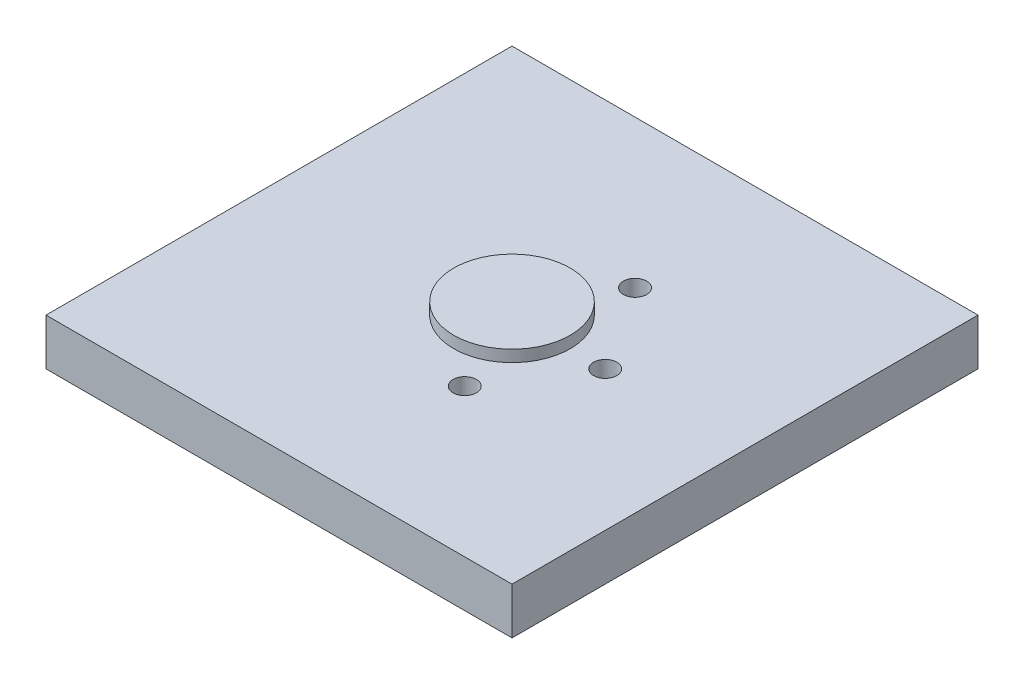
SolidWorks part; units mm, degrees
ref_plane "Front Plane" through (0, 0, 0) normal (0, 0, 1) x (1, 0, 0)
ref_plane "Top Plane" through (0, 0, 0) normal (0, 1, 0) x (1, 0, 0)
ref_plane "Right Plane" through (0, 0, 0) normal (1, 0, 0) x (0, 0, -1)
sketch "Sketch1" plane through (0, 0, 0) normal (0, 1, 0) x (1, 0, 0)
  line L1 (-63.5, 63.5) -> (63.5, 63.5)
  line L2 (-63.5, 63.5) -> (-63.5, -63.5)
  line L3 (-63.5, -63.5) -> (63.5, -63.5)
  line L4 (63.5, 63.5) -> (63.5, -63.5)
  line L5 (-63.5, 63.5) -> (63.5, -63.5) construction
  line L6 (-63.5, -63.5) -> (63.5, 63.5) construction
  point P0 (0, 0)
  dimension "D1" = 127
extrude "Boss-Extrude1" add sketch "Sketch1" along normal blind 12.7
sketch "Sketch3" plane through (0, 12.7, 0) normal (0, 1, 0) x (1, 0, 0)
  circle A0 centre (0, 0) radius 15.875
  dimension "D1" = 31.75
extrude "Boss-Extrude2" add sketch "Sketch3" along normal blind 3.175
hole_wizard "1/4 (0.25) Diameter Hole1" positions "Sketch5" profile "Sketch4" hole size "1/4" standard "ANSI Inch" end condition up to next
sketch "Sketch5" plane through (0, 12.7, 0) normal (0, 1, 0) x (1, 0, 0)
  line L0 (0, 0) -> (63.5, 0) construction
  line L1 (63.5, -63.5) -> (63.5, 63.5) construction
  line L4 (0, 0) -> (63.5, 142.6233) construction
  line L6 (0, 0) -> (63.5, -142.6233) construction
  circle A0 centre (0, 0) radius 25.4 construction
  point P0 (10.3311, 23.2041)
  point P2 (25.4, 0)
  point P4 (10.3311, -23.2041)
  dimension "D1" = 50.8
  dimension "D2" = 66
sketch "Sketch4" plane through (10.3311, 12.7, -23.2041) normal (1, 0, 0) x (0, 0, 1)
  line L0 (0, 0) -> (0, 12.7)
  line L1 (0, 12.7) -> (3.175, 12.7)
  line L2 (3.175, 12.7) -> (3.175, 0)
  line L5 (3.175, 0) -> (0, 0)
  line L11 (0, -6.35) -> (0, 107.95) construction
  dimension "Thru Hole Dia." = 6.35
  dimension "Thru Hole Depth" = 12.7
